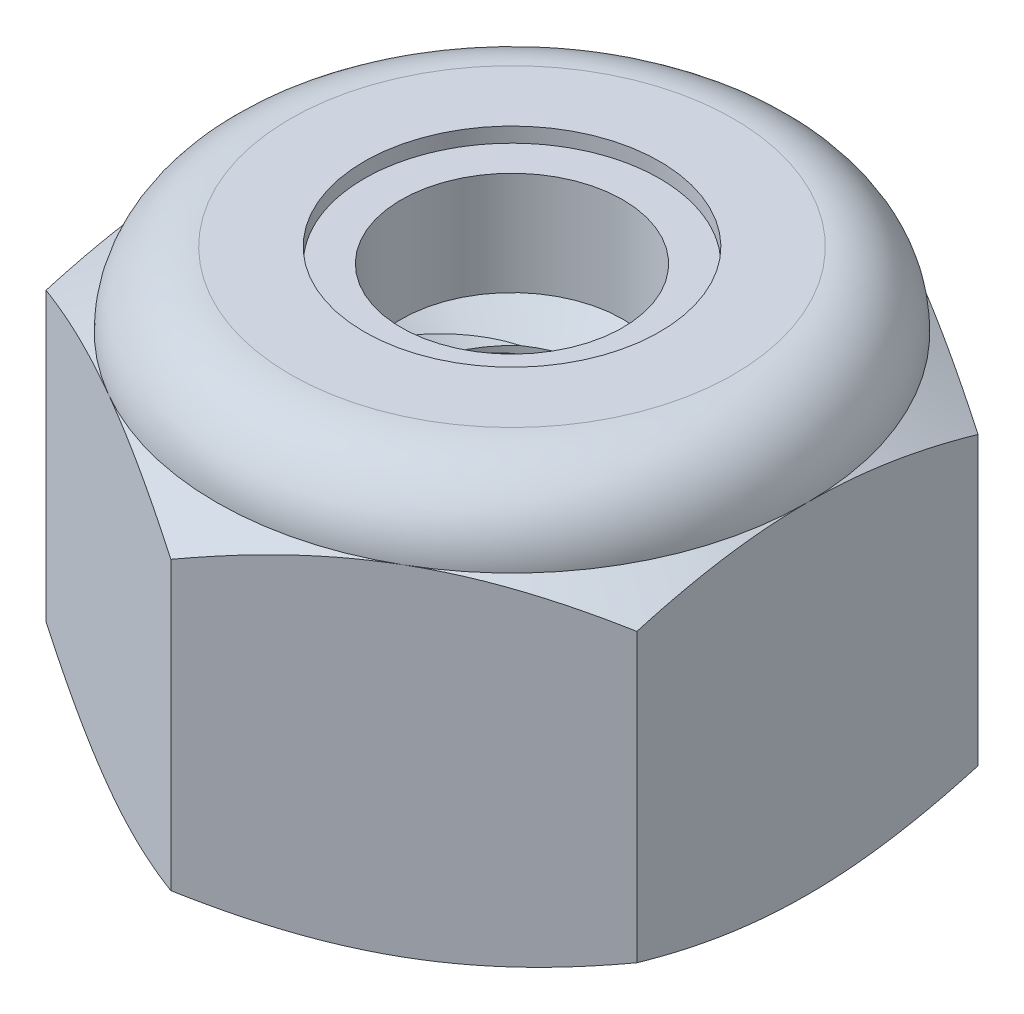
SolidWorks part; units mm, degrees
ref_plane "Front" through (0, 0, 0) normal (0, 0, 1) x (1, 0, 0)
ref_plane "Top" through (0, 0, 0) normal (0, 1, 0) x (1, 0, 0)
ref_plane "Right" through (0, 0, 0) normal (1, 0, 0) x (0, 0, -1)
sketch "Sketch1" plane through (0, 0, 0) normal (0, 1, 0) x (1, 0, 0)
  line L1 (0, 2.3094) -> (-2, 1.1547) construction
  line L2 (-2, 1.1547) -> (-2, -1.1547) construction
  line L3 (-2, -1.1547) -> (0, -2.3094) construction
  line L4 (0, -2.3094) -> (2, -1.1547) construction
  line L5 (2, -1.1547) -> (2, 1.1547) construction
  line L6 (2, 1.1547) -> (0, 2.3094) construction
  circle A0 centre (0, 0) radius 2 construction
  circle A1 centre (0, 0) radius 1 construction
  point P11 (0, -1)
  point P12 (0, 0)
  dimension "Thread Dia" = 2
  dimension "Width" = 4
sketch "Sketch2" plane through (0, 0, 0) normal (1, 0, 0) x (0, 0, -1)
  line L0 (-1, -1.4) -> (-1, 1.4) construction
  line L1 (0, 0) -> (0, 1.4) construction
  line L2 (0, 1.4) -> (-1, 1.4) construction
  line L3 (-1.0433, -1.375) -> (-0.6969, -1.575) construction
  line L4 (-0.6969, -1.575) -> (-1.0433, -1.775) construction
  line L5 (-1.0433, -1.775) -> (-1.0433, -1.375) construction
  line L6 (-0.7402, -1.55) -> (-0.7402, -1.6) construction
  line L7 (-1.0217, -1.575) -> (-1.0217, -1.3875) construction
  line L8 (-1, -1.4) -> (-1, -1.75) construction
  line L9 (-1.0433, -1.575) -> (-1, -1.575) construction
  line L10 (-0.7402, -1.575) -> (-0.6969, -1.575) construction
  line L11 (-1.0217, -1.575) -> (-1.0217, -1.7625) construction
  line L12 (-0.75, 0.6) -> (-0.75, 1.3) construction
  line L13 (-0.75, 1.3) -> (-1, 1.3) construction
  line L14 (-1, 1.3) -> (-1, 0.6) construction
  line L15 (-1, 0.6) -> (-0.75, 0.6) construction
  point P6 (-1, 0)
  point P25 (-0.75, 1.3)
  dimension "Height" = 2.8
  dimension "Pitch" = 0.4
  dimension "D2" = 0.05
  dimension "D1" = 0.25
  dimension "D3" = 0.7
  dimension "D4" = 0.1
sketch "Sketch3" plane through (0, 0, 0) normal (0, 1, 0) x (1, 0, 0)
  line L0 (0, 2.3094) -> (2, 1.1547)
  line L1 (2, 1.1547) -> (2, -1.1547)
  line L2 (2, -1.1547) -> (0, -2.3094)
  line L3 (0, -2.3094) -> (-2, -1.1547)
  line L4 (-2, -1.1547) -> (-2, 1.1547)
  line L5 (-2, 1.1547) -> (0, 2.3094)
sketch "Sketch7" plane through (0, 0, 0) normal (0, 1, 0) x (1, 0, 0)
  circle A0 centre (0, 0) radius 2 construction
  circle A1 centre (0, 0) radius 2
extrude "Boss-Extrude2" add sketch "Sketch3" along normal up to vertex (-1.4 mm away) and the other way up to vertex (1.4 mm away) up to point (0, -1.4, 1) other way up to point (0, -1.4, 1)
sketch "Sketch4" plane through (0, 0, 0) normal (0, 1, 0) x (1, 0, 0)
  circle A0 centre (0, 0) radius 1
  circle A1 centre (0, 0) radius 1 construction
extrude "Cut-Extrude4" cut sketch "Sketch4" along normal through all both and the other way through all
sketch "Sketch6" plane through (0, 0, 0) normal (1, 0, 0) x (0, 0, -1)
  line L0 (2, -1.4) -> (2, 1.4) construction
  line L7 (2, 1.4) -> (2, 0.9) construction
  line L8 (2, 1.4) -> (1.5, 1.4) construction
  line L11 (2, 0.9) -> (2.3094, 0.9)
  line L13 (2.3094, 0.9) -> (2.3094, 1.4)
  line L14 (2.3094, 1.4) -> (1.5, 1.4)
  arc A1 (2, 0.9) -> (1.5, 1.4) centre (1.5, 0.9) ccw
  point P15 (2, 0)
  dimension "D1" = 0.5
revolve "Cut-Revolve1" cut sketch "Sketch6" angle 360 about axis through (0, 1.4, 0) along (0, -1, 0)
extrude "Cut-Extrude5" cut sketch "Sketch7" against normal through all draft 60 from surface flip side to cut starting at face at (0, 0.9, -2.0138)
sketch "Sketch19" plane through (0, -1.4, 0) normal (0, -1, 0) x (1, 0, 0)
  circle A0 centre (0, 0) radius 2 construction
  circle A1 centre (0, 0) radius 2
extrude "Cut-Extrude6" cut sketch "Sketch19" against normal through all draft 60 flip side to cut
chamfer "Chamfer1" distance 0.15 angle 45 1 edges at (0, -1.4, 1)
sketch "Sketch24" plane through (0, 0, 0) normal (1, 0, 0) x (0, 0, -1)
  line L0 (-1, 1.3) -> (-0.75, 1.3)
  line L1 (-0.75, 1.3) -> (-0.75, 0.6)
  line L2 (-0.75, 0.6) -> (-1, 0.6)
  line L3 (-1, 0.6) -> (-1, 1.3)
revolve "Revolve1" add sketch "Sketch24" angle 360 about L1
ref_plane "Contact Plane 1" through (0, 1.4, 0) normal (0, 1, 0) x (1, 0, 0)
ref_plane "Contact Plane 2" through (0, -1.4, 0) normal (0, -1, 0) x (-1, 0, 0)
sketch "Sketch5" plane through (0, -1.4, 0) normal (0, 1, 0) x (1, 0, 0)
  circle A1 centre (0, 0) radius 1
  circle A2 centre (0, 0) radius 1 construction
curve "Helix/Spiral1" pitch 0.4 height 2.8 radius 1 centre (0, -1.4, 0) axis (0, 1, 0) start towards (0, 0, 1)
sketch "Sketch21" plane through (0, 0, 0) normal (1, 0, 0) x (0, 0, -1)
  line L0 (-1.0217, -1.3875) -> (-1.0217, -1.7625)
  line L1 (-1.0217, -1.7625) -> (-0.7402, -1.6)
  line L2 (-0.7402, -1.6) -> (-0.7402, -1.55)
  line L3 (-0.7402, -1.55) -> (-1.0217, -1.3875)
sweep "Sweep1" add profiles "Sketch21" path "Helix/Spiral1"
sketch "Sketch23" plane through (0, 0.6, 0) normal (0, 1, 0) x (1, 0, 0)
  line L0 (0, 0) -> (0, -1) construction
  circle A1 centre (0, 0) radius 1.0433
extrude "Cut-Extrude8" cut sketch "Sketch23" along normal through all and the other way through all draft 45
combine bodies "Combine1" operation type add bodies to combine 147 143
sketch "Sketch30" plane through (0, -1.4, 0) normal (0, -1, 0) x (1, 0, 0)
  circle A0 centre (0, 0) radius 1.15 construction
  circle A1 centre (0, 0) radius 1.15
extrude "Cut-Extrude12" cut sketch "Sketch30" along normal through all and the other way through all draft 45
equation "\"D2@Sketch2\" = \"Pitch@Sketch2\" / 8"
equation "\"D1@Sketch2\"=\"Pitch@Sketch2\"*.625"
equation "\"D3@Sketch2\"=\"Height@Sketch2\"/4"
equation "\"D4@Sketch2\"=\"Pitch@Sketch2\"/4"
equation "\"D4@Helix/Spiral1\"=\"Pitch@Sketch2\""
equation "\"D3@Helix/Spiral1\"=\"Height@Sketch2\""
equation "\"D1@Sketch6\"=\"Pitch@Sketch2\"*1.25"
equation "\"D1@Chamfer1\"=\"Pitch@Sketch2\"*.375"
